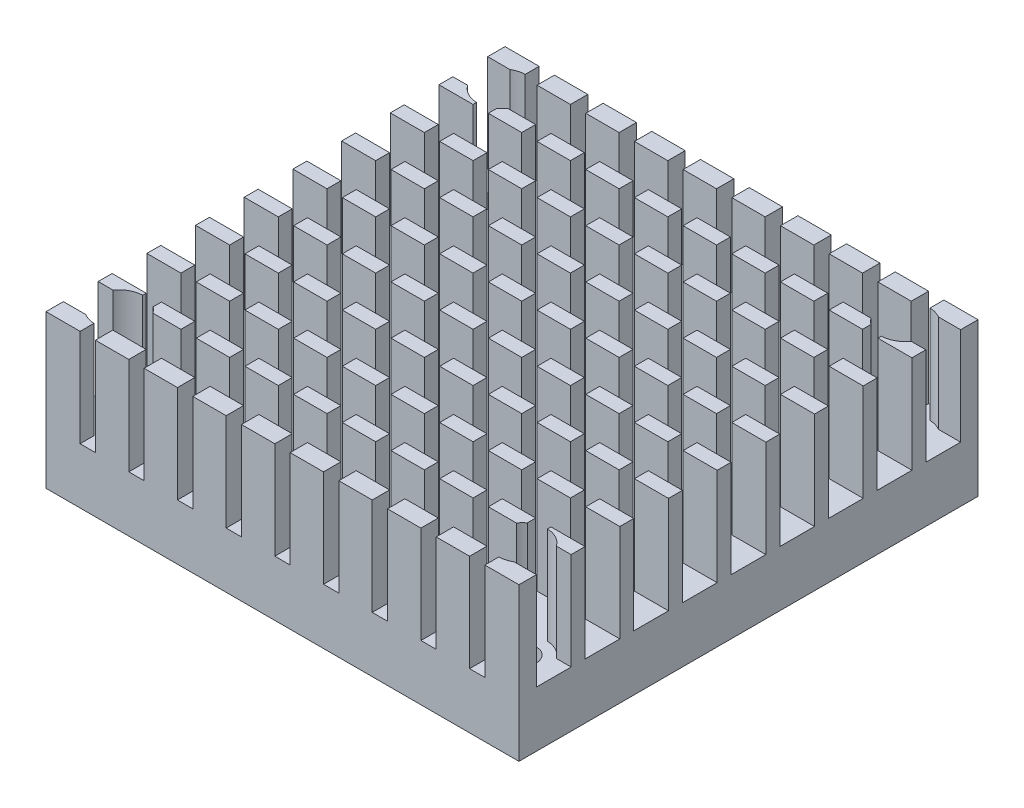
SolidWorks part; units mm, degrees
ref_plane "Plan de face" through (0, 0, 0) normal (0, 0, 1) x (1, 0, 0)
ref_plane "Plan de dessus" through (0, 0, 0) normal (0, 1, 0) x (1, 0, 0)
ref_plane "Plan de droite" through (0, 0, 0) normal (1, 0, 0) x (0, 0, -1)
sketch "Esquisse1" plane through (0, 0, 0) normal (0, 1, 0) x (1, 0, 0)
  line L1 (-17, -16.5) -> (17, -16.5)
  line L2 (-17, -16.5) -> (-17, 16.5)
  line L3 (-17, 16.5) -> (17, 16.5)
  line L4 (17, -16.5) -> (17, 16.5)
  line L5 (-17, -16.5) -> (17, 16.5) construction
  line L6 (-17, 16.5) -> (17, -16.5) construction
  point P0 (0, 0)
  dimension "D1" = 34
  dimension "D2" = 33
extrude "Boss.-Extru.1" add sketch "Esquisse1" along normal blind 11
sketch "Esquisse2" plane through (0, 11, 0) normal (0, 1, 0) x (1, 0, 0)
  line L0 (0, -17.5) -> (0, 17.5) construction
  line L1 (-0.55, -17.5) -> (-0.55, 17.5)
  line L2 (0.55, -17.5) -> (0.55, 17.5)
  line L3 (-3.5, -17.5) -> (-3.5, 17.5) construction
  line L4 (-4.05, -17.5) -> (-4.05, 17.5)
  line L5 (-2.95, -17.5) -> (-2.95, 17.5)
  line L6 (-7, -17.5) -> (-7, 17.5) construction
  line L7 (-7.55, -17.5) -> (-7.55, 17.5)
  line L8 (-6.45, -17.5) -> (-6.45, 17.5)
  line L9 (-10.5, -17.5) -> (-10.5, 17.5) construction
  line L10 (-11.05, -17.5) -> (-11.05, 17.5)
  line L11 (-9.95, -17.5) -> (-9.95, 17.5)
  line L12 (-14, -17.5) -> (-14, 17.5) construction
  line L13 (-14.55, -17.5) -> (-14.55, -15.4993)
  line L14 (-13.45, -17.5) -> (-13.45, -15.15)
  line L15 (0, -17.5) -> (-3.5, -17.5) construction
  line L16 (3.5, -17.5) -> (3.5, 17.5) construction
  line L17 (2.95, -17.5) -> (2.95, 17.5)
  line L18 (4.05, -17.5) -> (4.05, 17.5)
  line L19 (7, -17.5) -> (7, 17.5) construction
  line L20 (6.45, -17.5) -> (6.45, 17.5)
  line L21 (7.55, -17.5) -> (7.55, 17.5)
  line L22 (10.5, -17.5) -> (10.5, 17.5) construction
  line L23 (9.95, -17.5) -> (9.95, 17.5)
  line L24 (11.05, -17.5) -> (11.05, 17.5)
  line L25 (14, -17.5) -> (14, 17.5) construction
  line L26 (13.45, -17.5) -> (13.45, -15.15)
  line L27 (14.55, -17.5) -> (14.55, -15.4993)
  line L28 (0, -17.5) -> (3.5, -17.5) construction
  line L29 (-13.45, 15.15) -> (-13.45, 17.5)
  line L33 (-14.55, 15.4993) -> (-14.55, 17.5)
  line L34 (13.45, 15.15) -> (13.45, 17.5)
  line L38 (14.55, 15.4993) -> (14.55, 17.5)
  line L39 (13.45, -12.35) -> (13.45, 12.35)
  line L40 (14.55, -12.0007) -> (14.55, 12.0007)
  line L41 (-13.45, -12.35) -> (-13.45, 12.35)
  line L42 (-14.55, -12.0007) -> (-14.55, 12.0007)
  line L115 (-14, -17.5) -> (-14, 17.5) construction
  line L116 (-14.55, -17.5) -> (-14.55, 17.5)
  line L117 (-13.45, -17.5) -> (-13.45, 17.5)
  line L118 (14, -17.5) -> (14, 17.5) construction
  line L119 (13.45, -17.5) -> (13.45, 17.5)
  line L120 (14.55, -17.5) -> (14.55, 17.5)
  line L121 (-14, -17.5) -> (-14, 17.5) construction
  line L122 (-14.55, -17.5) -> (-14.55, 17.5)
  line L123 (-13.45, -17.5) -> (-13.45, 17.5)
  line L124 (14, -17.5) -> (14, 17.5) construction
  line L125 (13.45, -17.5) -> (13.45, 17.5)
  line L126 (14.55, -17.5) -> (14.55, 17.5)
  arc A0 (-0.55, -17.5) -> (0.55, -17.5) centre (0, -17.5) ccw
  arc A1 (0.55, 17.5) -> (-0.55, 17.5) centre (0, 17.5) ccw
  arc A2 (-4.05, -17.5) -> (-2.95, -17.5) centre (-3.5, -17.5) ccw
  arc A3 (-2.95, 17.5) -> (-4.05, 17.5) centre (-3.5, 17.5) ccw
  arc A4 (-7.55, -17.5) -> (-6.45, -17.5) centre (-7, -17.5) ccw
  arc A5 (-6.45, 17.5) -> (-7.55, 17.5) centre (-7, 17.5) ccw
  arc A6 (-11.05, -17.5) -> (-9.95, -17.5) centre (-10.5, -17.5) ccw
  arc A7 (-9.95, 17.5) -> (-11.05, 17.5) centre (-10.5, 17.5) ccw
  arc A8 (-14.55, -17.5) -> (-13.45, -17.5) centre (-14, -17.5) ccw
  arc A9 (-13.45, 17.5) -> (-14.55, 17.5) centre (-14, 17.5) ccw
  arc A10 (2.95, -17.5) -> (4.05, -17.5) centre (3.5, -17.5) ccw
  arc A11 (4.05, 17.5) -> (2.95, 17.5) centre (3.5, 17.5) ccw
  arc A12 (6.45, -17.5) -> (7.55, -17.5) centre (7, -17.5) ccw
  arc A13 (7.55, 17.5) -> (6.45, 17.5) centre (7, 17.5) ccw
  arc A14 (9.95, -17.5) -> (11.05, -17.5) centre (10.5, -17.5) ccw
  arc A15 (11.05, 17.5) -> (9.95, 17.5) centre (10.5, 17.5) ccw
  arc A16 (13.45, -17.5) -> (14.55, -17.5) centre (14, -17.5) ccw
  arc A17 (14.55, 17.5) -> (13.45, 17.5) centre (14, 17.5) ccw
  arc A18 (-14.55, -12.0007) -> (-14.55, -15.4993) centre (-14.5, -13.75) ccw
  arc A19 (13.45, -12.35) -> (13.45, -15.15) centre (14.5, -13.75) ccw
  arc A20 (13.45, 15.15) -> (13.45, 12.35) centre (14.5, 13.75) ccw
  arc A21 (-14.55, 15.4993) -> (-14.55, 12.0007) centre (-14.5, 13.75) ccw
  arc A24 (-13.45, 12.35) -> (-13.45, 15.15) centre (-14.5, 13.75) ccw
  arc A27 (14.55, 12.0007) -> (14.55, 15.4993) centre (14.5, 13.75) ccw
  arc A28 (14.55, -15.4993) -> (14.55, -12.0007) centre (14.5, -13.75) ccw
  arc A29 (-13.45, -15.15) -> (-13.45, -12.35) centre (-14.5, -13.75) ccw
  arc A82 (-14.55, -17.5) -> (-13.45, -17.5) centre (-14, -17.5) ccw
  arc A83 (-13.45, 17.5) -> (-14.55, 17.5) centre (-14, 17.5) ccw
  arc A84 (13.45, -17.5) -> (14.55, -17.5) centre (14, -17.5) ccw
  arc A85 (14.55, 17.5) -> (13.45, 17.5) centre (14, 17.5) ccw
  point P2 (0, 0)
  point P12 (-3.5, 0)
  point P19 (-7, 0)
  point P26 (-10.5, 0)
  point P33 (-14, 0)
  point P41 (3.5, 0)
  point P48 (7, 0)
  point P55 (10.5, 0)
  point P62 (14, 0)
  point P83 (-14, 0)
  point P93 (14, 0)
  point P109 (-14, 0)
  point P116 (14, 0)
  point P123 (-14, 0)
  point P130 (14, 0)
  point P137 (-14, 0)
  point P144 (14, 0)
  point P151 (-14, 0)
  point P158 (14, 0)
  point P165 (-14, 0)
  point P172 (14, 0)
  point P179 (-14, 0)
  point P186 (14, 0)
  point P193 (-14, 0)
  point P200 (14, 0)
  point P207 (-14, 0)
  point P214 (14, 0)
  point P221 (-14, 0)
  point P228 (14, 0)
  point P235 (-14, 0)
  point P242 (14, 0)
  point P249 (-14, 0)
  point P256 (14, 0)
  point P263 (-14, 0)
  point P270 (14, 0)
  point P277 (-14, 0)
  point P284 (14, 0)
  point P291 (-14, 0)
  point P298 (14, 0)
  dimension "D1" = 5
  dimension "D6" = 3.5
  dimension "D3" = 1.1
  dimension "D2" = 3.5
  dimension "D5" = 3.5
  dimension "D4" = 5
extrude "Enlèv. mat.-Extru.1" cut sketch "Esquisse2" against normal blind 7
sketch "Esquisse3" plane through (0, 11, 0) normal (0, 1, 0) x (1, 0, 0)
  line L0 (18.8405, 0) -> (-18.8405, 0) construction
  line L1 (18.8405, -1.25) -> (-18.8405, -1.25)
  line L2 (18.8405, 1.25) -> (-18.8405, 1.25)
  line L3 (18.8405, 3.5) -> (-18.8405, 3.5) construction
  line L4 (18.8405, 2.25) -> (-18.8405, 2.25)
  line L5 (18.8405, 4.75) -> (-18.8405, 4.75)
  line L6 (18.8405, 7) -> (-18.8405, 7) construction
  line L7 (18.8405, 5.75) -> (-18.8405, 5.75)
  line L8 (18.8405, 8.25) -> (-18.8405, 8.25)
  line L9 (18.8405, 10.5) -> (-18.8405, 10.5) construction
  line L10 (18.8405, 9.25) -> (-18.8405, 9.25)
  line L11 (18.8405, 11.75) -> (-18.8405, 11.75)
  line L12 (18.8405, 14) -> (-18.8405, 14) construction
  line L13 (18.8405, 12.75) -> (-18.8405, 12.75)
  line L14 (18.8405, 15.25) -> (-18.8405, 15.25)
  line L15 (18.8405, 0) -> (18.8405, 3.5) construction
  line L16 (18.8405, -3.5) -> (-18.8405, -3.5) construction
  line L17 (18.8405, -4.75) -> (-18.8405, -4.75)
  line L18 (18.8405, -2.25) -> (-18.8405, -2.25)
  line L19 (18.8405, -7) -> (-18.8405, -7) construction
  line L20 (18.8405, -8.25) -> (-18.8405, -8.25)
  line L21 (18.8405, -5.75) -> (-18.8405, -5.75)
  line L22 (18.8405, -10.5) -> (-18.8405, -10.5) construction
  line L23 (18.8405, -11.75) -> (-18.8405, -11.75)
  line L24 (18.8405, -9.25) -> (-18.8405, -9.25)
  line L25 (18.8405, -14) -> (-18.8405, -14) construction
  line L26 (18.8405, -15.25) -> (-18.8405, -15.25)
  line L27 (18.8405, -12.75) -> (-18.8405, -12.75)
  arc A0 (18.8405, -1.25) -> (18.8405, 1.25) centre (18.8405, 0) ccw
  arc A1 (-18.8405, 1.25) -> (-18.8405, -1.25) centre (-18.8405, 0) ccw
  arc A2 (18.8405, 2.25) -> (18.8405, 4.75) centre (18.8405, 3.5) ccw
  arc A3 (-18.8405, 4.75) -> (-18.8405, 2.25) centre (-18.8405, 3.5) ccw
  arc A4 (18.8405, 5.75) -> (18.8405, 8.25) centre (18.8405, 7) ccw
  arc A5 (-18.8405, 8.25) -> (-18.8405, 5.75) centre (-18.8405, 7) ccw
  arc A6 (18.8405, 9.25) -> (18.8405, 11.75) centre (18.8405, 10.5) ccw
  arc A7 (-18.8405, 11.75) -> (-18.8405, 9.25) centre (-18.8405, 10.5) ccw
  arc A8 (18.8405, 12.75) -> (18.8405, 15.25) centre (18.8405, 14) ccw
  arc A9 (-18.8405, 15.25) -> (-18.8405, 12.75) centre (-18.8405, 14) ccw
  arc A10 (18.8405, -4.75) -> (18.8405, -2.25) centre (18.8405, -3.5) ccw
  arc A11 (-18.8405, -2.25) -> (-18.8405, -4.75) centre (-18.8405, -3.5) ccw
  arc A12 (18.8405, -8.25) -> (18.8405, -5.75) centre (18.8405, -7) ccw
  arc A13 (-18.8405, -5.75) -> (-18.8405, -8.25) centre (-18.8405, -7) ccw
  arc A14 (18.8405, -11.75) -> (18.8405, -9.25) centre (18.8405, -10.5) ccw
  arc A15 (-18.8405, -9.25) -> (-18.8405, -11.75) centre (-18.8405, -10.5) ccw
  arc A16 (18.8405, -15.25) -> (18.8405, -12.75) centre (18.8405, -14) ccw
  arc A17 (-18.8405, -12.75) -> (-18.8405, -15.25) centre (-18.8405, -14) ccw
  point P2 (0, 0)
  point P11 (0, 3.5)
  point P18 (0, 7)
  point P25 (0, 10.5)
  point P32 (0, 14)
  point P41 (0, -3.5)
  point P48 (0, -7)
  point P55 (0, -10.5)
  point P62 (0, -14)
  dimension "D1" = 2.5
  dimension "D3" = 3.5
  dimension "D2" = 5
  dimension "D4" = 5
extrude "Enlèv. mat.-Extru.2" cut sketch "Esquisse3" against normal blind 7
ref_axis "Axe1" through (0, -2.2976, 0) along (0, 1, 0)
sketch "Esquisse4" plane through (0, 4, 0) normal (0, 1, 0) x (1, 0, 0)
  circle A0 centre (-14.5, 13.75) radius 1
  circle A1 centre (14.5, 13.75) radius 1
  circle A2 centre (14.5, -13.75) radius 1
  circle A3 centre (-14.5, -13.75) radius 1
  dimension "D1" = 2
extrude "Enlèv. mat.-Extru.3" cut sketch "Esquisse4" against normal up to next
